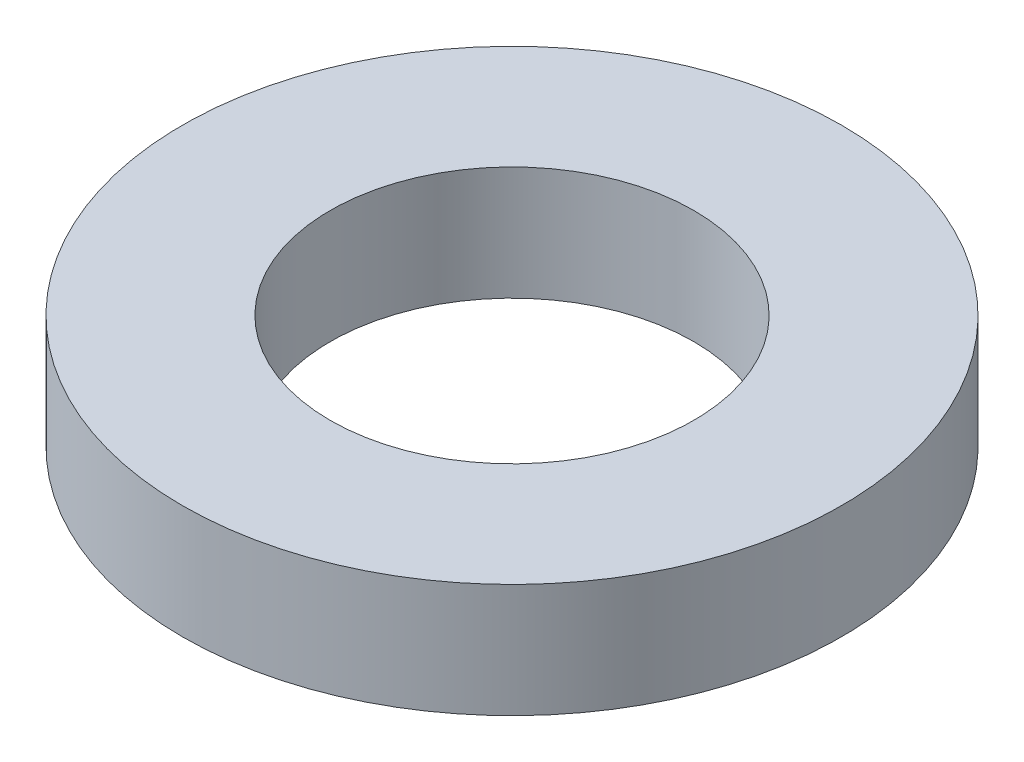
SolidWorks part; units mm, degrees
ref_plane "Front Plane" through (0, 0, 0) normal (0, 0, 1) x (1, 0, 0)
ref_plane "Top Plane" through (0, 0, 0) normal (0, 1, 0) x (1, 0, 0)
ref_plane "Right Plane" through (0, 0, 0) normal (1, 0, 0) x (0, 0, -1)
sketch "Sketch1" plane through (0, 0, 0) normal (0, 1, 0) x (1, 0, 0)
  circle A0 centre (0, 0) radius 72.5
  dimension "FLANGE_OD" = 145
extrude "Boss-Extrude1" add sketch "Sketch1" along normal blind 25
sketch "Sketch2" plane through (0, 0, 0) normal (0, 1, 0) x (1, 0, 0)
  circle A0 centre (0, 0) radius 40
  dimension "BORE_D" = 80
extrude "Cut-Extrude1" cut sketch "Sketch2" along normal through all
sketch "Sketch3" plane through (0, 25, 0) normal (0, 1, 0) x (1, 0, 0)
  circle A0 centre (0, 0) radius 28.7494 construction
  circle A1 centre (-28.7494, 0) radius 5.7972
  dimension "BOLT_D" = 11.5945
  dimension "BOLT_PCD" = 57.4987
extrude "Cut-Extrude2" cut sketch "Sketch3" against normal blind 17.5117 rebuild error yes
pattern_circular "CirPattern1" count 3 over 360 rebuild error yes
